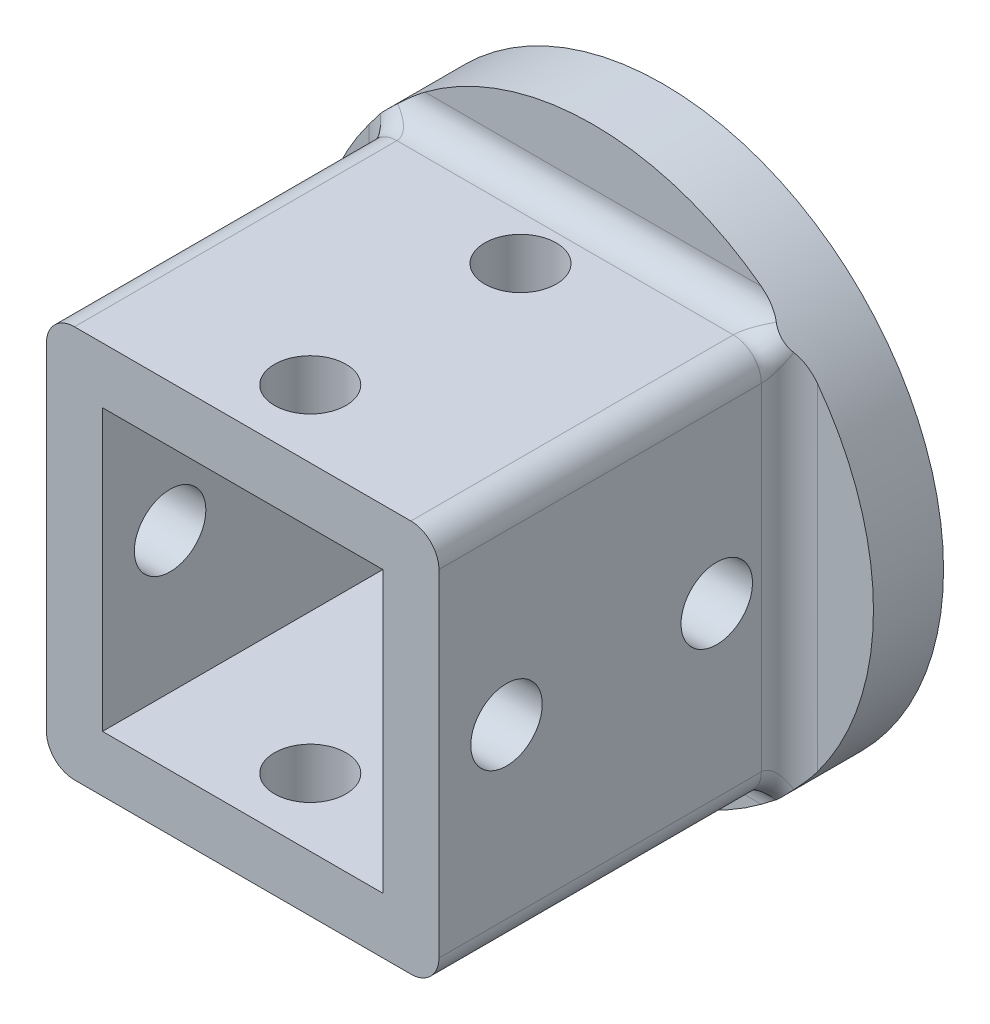
SolidWorks part; units mm, degrees
ref_plane "前视基准面" through (0, 0, 0) normal (0, 0, 1) x (1, 0, 0)
ref_plane "上视基准面" through (0, 0, 0) normal (0, 1, 0) x (1, 0, 0)
ref_plane "右视基准面" through (0, 0, 0) normal (1, 0, 0) x (0, 0, -1)
sketch "草图1" plane through (0, 0, 0) normal (0, 0, 1) x (1, 0, 0)
  circle A0 centre (0, 0) radius 20
  dimension "D1" = 40
extrude "凸台-拉伸1" add sketch "草图1" along normal blind 5
sketch "草图2" plane through (0, 0, 5) normal (0, 0, 1) x (1, 0, 0)
  line L1 (4.95, -4.95) -> (-4.95, -4.95) construction
  line L2 (4.95, -4.95) -> (4.95, 4.95) construction
  line L3 (4.95, 4.95) -> (-4.95, 4.95) construction
  line L4 (-4.95, -4.95) -> (-4.95, 4.95) construction
  line L5 (4.95, -4.95) -> (-4.95, 4.95) construction
  line L6 (4.95, 4.95) -> (-4.95, -4.95) construction
  circle A0 centre (-4.95, 4.95) radius 1.5
  circle A1 centre (4.95, 4.95) radius 1.5
  circle A2 centre (-4.95, -4.95) radius 1.5
  circle A3 centre (4.95, -4.95) radius 1.5
  point P0 (0, 0)
  dimension "D3" = 3
  dimension "D4" = 3
  dimension "D5" = 3
  dimension "D6" = 3
  dimension "D1" = 9.9
  dimension "D2" = 9.9
extrude "切除-拉伸1" cut sketch "草图2" against normal blind 5
sketch "草图4" plane through (0, 0, 5) normal (0, 0, 1) x (1, 0, 0)
  line L5 (-10, 10) -> (10, 10)
  line L23 (-10, 10) -> (-10, -10)
  line L27 (-10, -10) -> (10, -10)
  line L28 (10, 10) -> (10, -10)
  line L33 (-10, 10) -> (10, -10) construction
  line L34 (-10, -10) -> (10, 10) construction
  line L35 (-14, 14) -> (14, 14)
  line L36 (-14, 14) -> (-14, -14)
  line L37 (-14, -14) -> (14, -14)
  line L38 (14, 14) -> (14, -14)
  line L39 (-14, 14) -> (14, -14) construction
  line L40 (-14, -14) -> (14, 14) construction
  point P0 (0, 0)
  point P5 (0, 0)
  dimension "D1" = 20
  dimension "D2" = 28
extrude "凸台-拉伸3" add sketch "草图4" along normal blind 25 contours L38 L35 L36 L37 L5 L28 L27 L23 region at (0, 13.604, 5)
sketch "草图5" plane through (-14, 0, 0) normal (-1, 0, 0) x (0, 0, 1)
  line L0 (30.0014, 0) -> (0, 0) construction
  line L2 (0, 20) -> (0, -20) construction
  circle A0 centre (10.1786, 0) radius 2.55
  circle A1 centre (25.1786, 0) radius 2.55
  circle A2 centre (40.1786, 0) radius 2.55
  dimension "D1" = 3
  dimension "D2" = 5.1
extrude "切除-拉伸2" cut sketch "草图5" against normal through all
sketch "草图6" plane through (0, 14, 0) normal (0, 1, 0) x (1, 0, 0)
  line L0 (0, -5) -> (0, -10.18) construction
  line L2 (-14, -5) -> (14, -5) construction
  circle A0 centre (0, -10.18) radius 2.55
  circle A1 centre (0, -25.18) radius 2.55
  circle A2 centre (0, -40.18) radius 2.55
  dimension "D2" = 5.1
  dimension "D3" = 3
extrude "切除-拉伸3" cut sketch "草图6" against normal through all
fillet "圆角1" radius 2 4 edges at (14, 0, 5) (0, 14, 5) (-14, 0, 5) (0, -14, 5)
fillet "圆角2" radius 2 8 edges at (14.0359, 14.0359, 6.623) (14.0359, -14.0359, 6.623) (-14.0359, -14.0359, 6.623) (-14.0359, 14.0359, 6.623) (14, 14, 18.5) (14, -14, 18.5) (-14, -14, 18.5) (-14, 14, 18.5)
